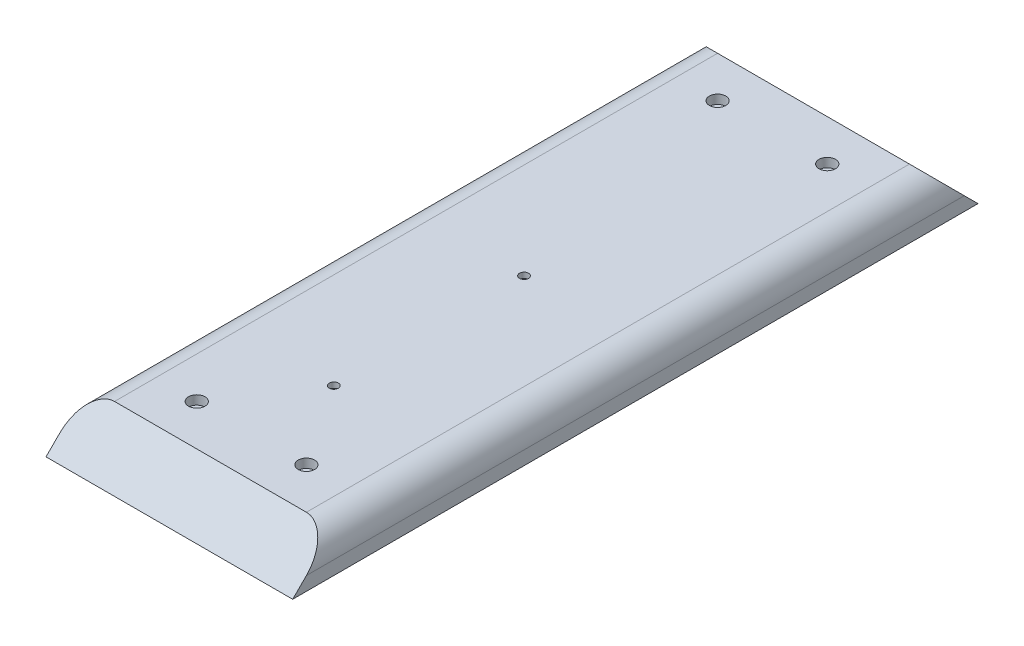
SolidWorks part; units mm, degrees
ref_plane "Front Plane" through (0, 0, 0) normal (0, 0, 1) x (1, 0, 0)
ref_plane "Top Plane" through (0, 0, 0) normal (0, 1, 0) x (1, 0, 0)
ref_plane "Right Plane" through (0, 0, 0) normal (1, 0, 0) x (0, 0, -1)
sketch "Sketch1" plane through (0, 0, 0) normal (0, 1, 0) x (1, 0, 0)
  line L1 (0, 0) -> (90, 0)
  line L2 (0, 0) -> (0, 250)
  line L3 (0, 250) -> (90, 250)
  line L4 (90, 0) -> (90, 250)
  dimension "D1" = 90
  dimension "D2" = 250
extrude "Boss-Extrude1" add sketch "Sketch1" along normal blind 15
chamfer "Chamfer1" distance 15 angle 45 2 edges at (45, 15, 0) (45, 15, -250)
fillet "Fillet1" radius 10 2 edges at (0, 15, -125) (90, 15, -125)
sketch "Sketch2" plane through (0, 15, 0) normal (0, 1, 0) x (1, 0, 0)
  line L0 (45, 0) -> (45, 30) construction
  line L1 (0, 0) -> (90, 0) construction
  line L2 (25, 30) -> (65, 30) construction
  line L3 (0, 125) -> (90, 125) construction
  line L4 (0, 5) -> (0, 245) construction
  line L5 (90, 245) -> (90, 5) construction
  circle A0 centre (25, 30) radius 1.65
  circle A1 centre (65, 30) radius 1.65
  circle A2 centre (65, 220) radius 1.65
  circle A3 centre (25, 220) radius 1.65
  point P6 (45, 30)
  dimension "D2" = 3.3
  dimension "D1" = 30
  dimension "D3" = 40
extrude "Cut-Extrude1" cut sketch "Sketch2" against normal through all
sketch "Sketch3" plane through (0, 15, 0) normal (0, 1, 0) x (1, 0, 0)
  line L0 (0, 125) -> (90, 125) construction
  line L1 (0, 5) -> (0, 245) construction
  line L2 (90, 245) -> (90, 5) construction
  circle A0 centre (25, 30) radius 3
  circle A1 centre (65, 30) radius 3
  circle A2 centre (65, 220) radius 3
  circle A3 centre (25, 220) radius 3
  dimension "D1" = 6
extrude "Cut-Extrude2" cut sketch "Sketch3" against normal blind 3.3
sketch "Sketch4" plane through (0, 15, 0) normal (0, 1, 0) x (1, 0, 0)
  line L0 (45, 0) -> (45, 250) construction
  line L1 (0, 0) -> (90, 0) construction
  line L2 (90, 250) -> (0, 250) construction
  line L3 (45, 60) -> (45, 129.4) construction
  circle A0 centre (45, 60) radius 1.65
  circle A1 centre (45, 129.4) radius 1.65
  dimension "D3" = 3.3
  dimension "D1" = 69.4
  dimension "D2" = 60
extrude "Cut-Extrude3" cut sketch "Sketch4" against normal through all
sketch "Sketch5" plane through (0, 0, 0) normal (0, -1, 0) x (1, 0, 0)
  line L1 (48.2332, -60) -> (46.6166, -57.2)
  line L2 (46.6166, -57.2) -> (43.3834, -57.2)
  line L3 (43.3834, -57.2) -> (41.7668, -60)
  line L4 (41.7668, -60) -> (43.3834, -62.8)
  line L5 (43.3834, -62.8) -> (46.6166, -62.8)
  line L6 (46.6166, -62.8) -> (48.2332, -60)
  line L7 (48.2332, -129.4) -> (46.6166, -126.6)
  line L8 (46.6166, -126.6) -> (43.3834, -126.6)
  line L9 (43.3834, -126.6) -> (41.7668, -129.4)
  line L10 (41.7668, -129.4) -> (43.3834, -132.2)
  line L11 (43.3834, -132.2) -> (46.6166, -132.2)
  line L12 (46.6166, -132.2) -> (48.2332, -129.4)
  circle A0 centre (45, -60) radius 2.8 construction
  circle A1 centre (45, -129.4) radius 2.8 construction
  dimension "D1" = 5.6
  dimension "D2" = 5.6
extrude "Cut-Extrude5" cut sketch "Sketch5" against normal offset from surface (13 mm away) 2 up to face at (45, 15, -58.35)
sketch "Sketch6" plane through (0, 0, 0) normal (0, -1, 0) x (1, 0, 0)
  line L0 (12.5, 0) -> (77.5, 0) construction
  line L1 (0, -162.5) -> (90, -162.5) construction
  line L2 (0, -97.5) -> (90, -97.5)
  line L3 (0, -97.5) -> (90, -97.5) construction
  line L4 (0, -227.5) -> (90, -227.5) construction
  line L5 (0, 0) -> (90, 0) construction
  line L6 (12.5, 0) -> (12.5, -250) construction
  line L7 (0, 0) -> (90, 0) construction
  line L8 (90, -250) -> (0, -250) construction
  line L9 (77.5, 0) -> (77.5, -250) construction
  circle A0 centre (12.5, -97.5) radius 3.125
  circle A1 centre (77.5, -97.5) radius 3.125
  circle A2 centre (77.5, -162.5) radius 3.125
  circle A3 centre (12.5, -162.5) radius 3.125
  circle A4 centre (12.5, -227.5) radius 3.125
  circle A5 centre (77.5, -227.5) radius 3.125
  point P10 (45, 0)
  point P11 (45, 0)
  dimension "D5" = 6.25
  dimension "D4" = 65
  dimension "D1" = 97.5
  dimension "D2" = 65
  dimension "D3" = 65
extrude "Cut-Extrude6" cut sketch "Sketch6" against normal blind 4
sketch "Sketch7" plane through (0, 0, 0) normal (0, -1, 0) x (1, 0, 0)
  line L0 (90, -250) -> (0, -250) construction
  line L1 (20, -101) -> (70, -101)
  line L2 (20, -101) -> (20, -214)
  line L3 (20, -214) -> (70, -214)
  line L4 (70, -101) -> (70, -214)
  line L5 (45, -250) -> (45, 0) construction
  line L6 (0, 0) -> (90, 0) construction
  point P10 (18.3689, -214)
  point P11 (45, -214)
  dimension "D1" = 36
  dimension "D2" = 113
  dimension "D3" = 50
extrude "Cut-Extrude7" cut sketch "Sketch7" against normal blind 10
fillet "Fillet2" radius 5 4 edges at (70, 5, -214) (20, 5, -214) (20, 5, -101) (70, 5, -101)
